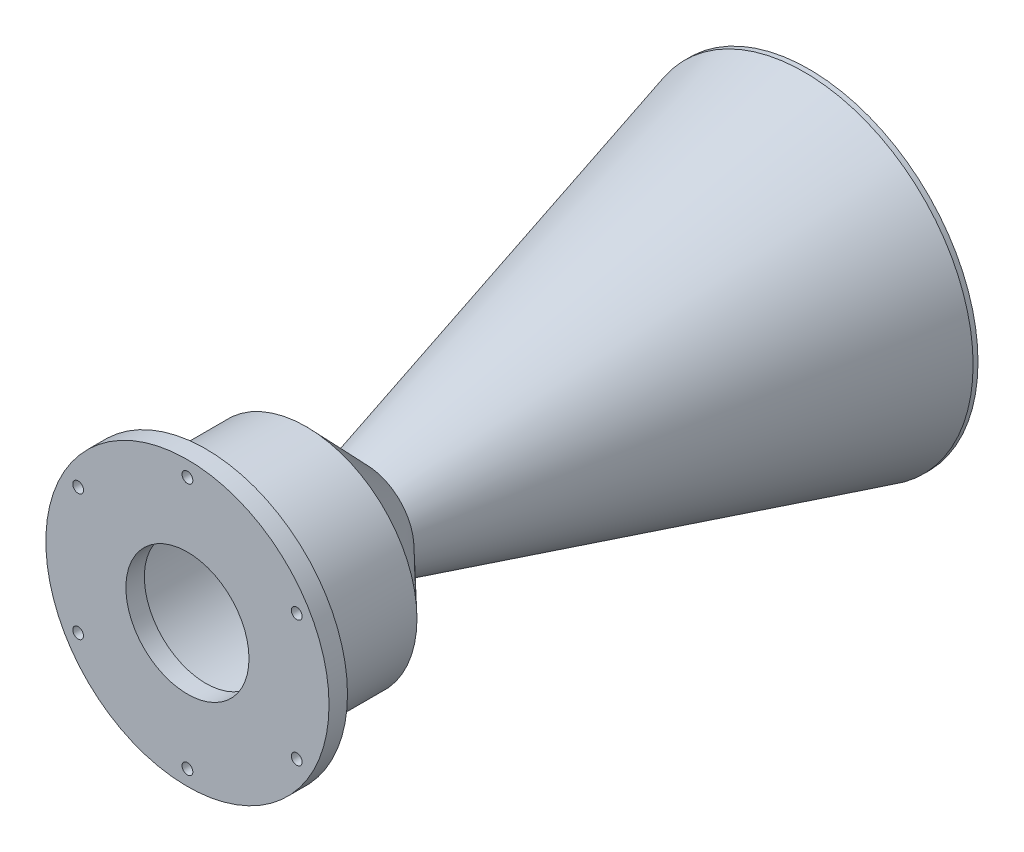
SolidWorks part; units mm, degrees
material "6061 Alloy"
ref_plane "Front Plane" through (0, 0, 0) normal (0, 0, 1) x (1, 0, 0)
ref_plane "Top Plane" through (0, 0, 0) normal (0, 1, 0) x (1, 0, 0)
ref_plane "Right Plane" through (0, 0, 0) normal (1, 0, 0) x (0, 0, -1)
sketch "Nozzle base structure" plane through (0, 0, 0) normal (1, 0, 0) x (0, 0, -1)
  line L0 (0, 0) -> (72.97, 0) construction
  line L1 (0, 0) -> (0, 4.5) construction
  line L2 (72.97, 0) -> (72.97, 24.553) construction
  line L3 (0, 4.5) -> (72.97, 24.553)
  line L4 (0, 0) -> (-25, 0) construction
  line L5 (-25, 0) -> (-25, 15) construction
  line L6 (-25, 15) -> (-10, 15)
  line L7 (-10, 15) -> (0, 4.5)
  line L8 (-28, 0) -> (-28, 18) construction
  line L9 (-28, 18) -> (-8.7143, 18) construction
  line L10 (-8.7143, 18) -> (0.9351, 7.8682)
  line L11 (0.9351, 7.8682) -> (72.175, 27.4458)
  line L12 (-28, 0) -> (-25, 0) construction
  line L13 (72.97, 24.553) -> (72.97, 27.4458)
  line L14 (72.97, 27.4458) -> (72.175, 27.4458)
  line L15 (-28, 10) -> (-25, 10)
  line L16 (-25, 15) -> (-25, 10)
  line L17 (-28, 18) -> (-28, 10)
  line L18 (-25, 15) -> (-25, 18) construction
  line L19 (-8.7143, 18) -> (-25, 18)
  line L20 (-25, 18) -> (-25, 23)
  line L21 (-25, 23) -> (-28, 23)
  line L22 (-28, 23) -> (-28, 18)
  dimension "D1" = 72.97
  dimension "D2" = 4.5
  dimension "D3" = 24.553
  dimension "D4" = 25
  dimension "D5" = 15
  dimension "D6" = 15
  dimension "D7" = 3
  dimension "D8" = 5
  dimension "D9" = 5
revolve "Revolve1" add sketch "Nozzle base structure" angle 360 about L0
fillet "Throat" radius 10 1 edges at (4.5, 0, 0) conic rho 0.65
sketch "Sketch2" plane through (0, 0, 25) normal (0, 0, -1) x (-1, 0, 0)
  line L0 (0, 0) -> (0, 23) construction
  line L1 (0, 23) -> (0, 18) construction
  circle A0 centre (0, 0) radius 23 construction
  circle A1 centre (0, 0) radius 18 construction
  circle A2 centre (0, 20.5) radius 0.875
  dimension "D1" = 1.75
extrude "Bolt hole" cut sketch "Sketch2" along direction (0, 0, -1) on the side against the normal up to next (3 mm away)
pattern_circular "Bolt hole pattern" count 6 over 360 about axis through (0, 0, 28) along (0, 0, 1) of "Bolt hole"
